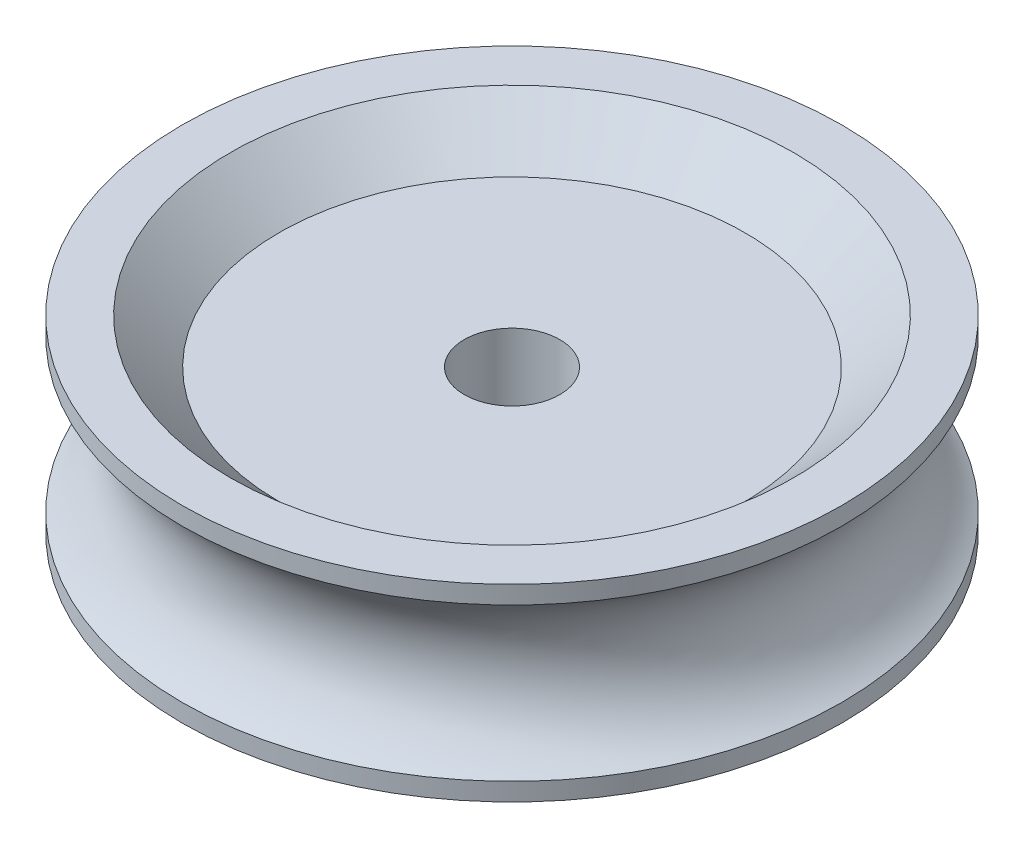
SolidWorks part; units mm, degrees
ref_plane "Спереди" through (0, 0, 0) normal (0, 0, 1) x (1, 0, 0)
ref_plane "Сверху" through (0, 0, 0) normal (0, 1, 0) x (1, 0, 0)
ref_plane "Справа" through (0, 0, 0) normal (1, 0, 0) x (0, 0, -1)
sketch "Эскиз1" plane through (0, 0, 0) normal (0, 0, 1) x (1, 0, 0)
  line L0 (8, 8.2533) -> (8, -8.2533)
  line L1 (8, -8.2533) -> (39.0128, -8.2533)
  line L2 (39.0128, -8.2533) -> (47.1858, -15.7848)
  line L3 (47.1858, -15.7848) -> (55.2303, -15.7848)
  line L4 (-50.7153, 0) -> (148.2535, 0) construction
  line L5 (55.2303, 15.7848) -> (55.2303, 12.7848)
  line L6 (47.1858, 15.7848) -> (55.2303, 15.7848)
  line L7 (39.0128, 8.2533) -> (47.1858, 15.7848)
  line L8 (55.2303, -15.7848) -> (55.2303, -12.7848)
  line L9 (8, 8.2533) -> (39.0128, 8.2533)
  line L10 (0, 40.9325) -> (0, -32.1466) construction
  arc A0 (55.2303, 12.7848) -> (55.2303, -12.7848) centre (63.0756, 0) ccw
  point P13 (8, 0)
  point P15 (8, 0)
  point P16 (85.8823, 24.3079)
  dimension "D2" = 15
  dimension "D1" = 3
revolve "Повернуть1" add sketch "Эскиз1" angle 360 about L10
